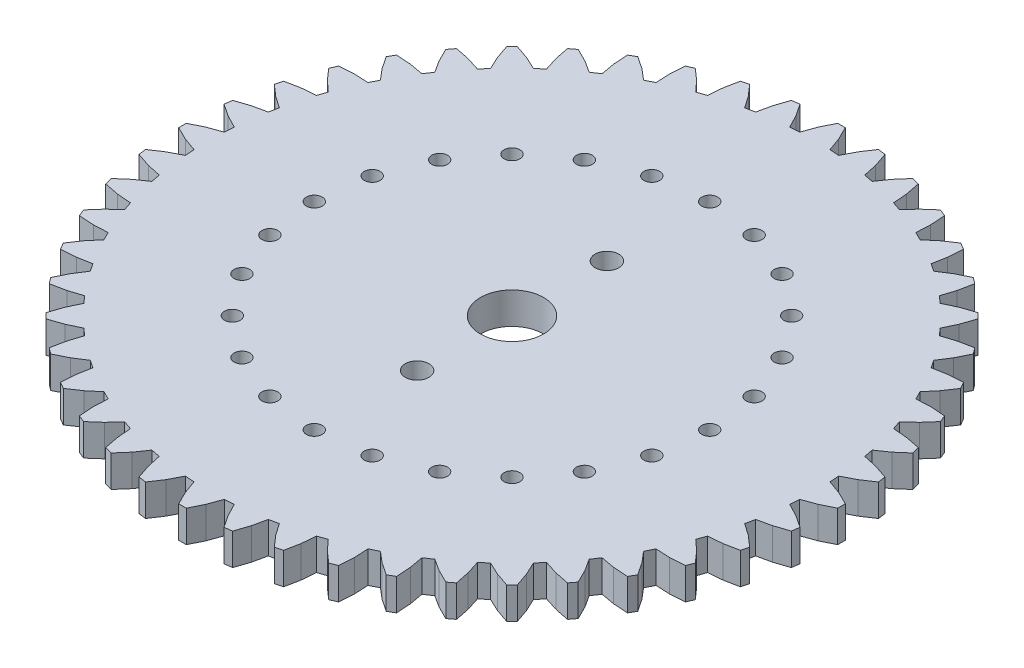
SolidWorks part; units mm, degrees
material "Brass"
ref_plane "Front Plane" through (0, 0, 0) normal (0, 0, 1) x (1, 0, 0)
ref_plane "Top Plane" through (0, 0, 0) normal (0, 1, 0) x (1, 0, 0)
ref_plane "Right Plane" through (0, 0, 0) normal (1, 0, 0) x (0, 0, -1)
sketch "Sketch5" plane through (0, 0, 0) normal (0, 1, 0) x (1, 0, 0)
  line L0 (87.3464, 51.4964) -> (89.0397, 50.8872)
  line L1 (89.0397, 50.8872) -> (90.7249, 50.062)
  line L2 (90.7249, 50.062) -> (90.7249, 49.095)
  line L3 (90.7249, 49.095) -> (89.0397, 48.2698)
  line L4 (89.0397, 48.2698) -> (87.3464, 47.6606)
  line L5 (87.3464, 47.6606) -> (87.2693, 46.4828)
  line L6 (87.2693, 46.4828) -> (88.8685, 45.6578)
  line L7 (88.8685, 45.6578) -> (90.4317, 44.6196)
  line L8 (90.4317, 44.6196) -> (90.3054, 43.6609)
  line L9 (90.3054, 43.6609) -> (88.5268, 43.0627)
  line L10 (88.5268, 43.0627) -> (86.7686, 42.6797)
  line L11 (86.7686, 42.6797) -> (86.5383, 41.5221)
  line L12 (86.5383, 41.5221) -> (88.0162, 40.4955)
  line L13 (88.0162, 40.4955) -> (89.4304, 39.2621)
  line L14 (89.4304, 39.2621) -> (89.1801, 38.328)
  line L15 (89.1801, 38.328) -> (87.3386, 37.9672)
  line L16 (87.3386, 37.9672) -> (85.5454, 37.8169)
  line L17 (85.5454, 37.8169) -> (85.1661, 36.6994)
  line L18 (85.1661, 36.6994) -> (86.4974, 35.4884)
  line L19 (86.4974, 35.4884) -> (87.7385, 34.0811)
  line L20 (87.7385, 34.0811) -> (87.3685, 33.1877)
  line L21 (87.3685, 33.1877) -> (85.4956, 33.0702)
  line L22 (85.4956, 33.0702) -> (83.6981, 33.1553)
  line L23 (83.6981, 33.1553) -> (83.1762, 32.0968)
  line L24 (83.1762, 32.0968) -> (84.3379, 30.7226)
  line L25 (84.3379, 30.7226) -> (85.3848, 29.1653)
  line L26 (85.3848, 29.1653) -> (84.9013, 28.3278)
  line L27 (84.9013, 28.3278) -> (83.0292, 28.4557)
  line L28 (83.0292, 28.4557) -> (81.2581, 28.7747)
  line L29 (81.2581, 28.7747) -> (80.6024, 27.7935)
  line L30 (80.6024, 27.7935) -> (81.575, 26.2794)
  line L31 (81.575, 26.2794) -> (82.4096, 24.5987)
  line L32 (82.4096, 24.5987) -> (81.821, 23.8315)
  line L33 (81.821, 23.8315) -> (79.9815, 24.2028)
  line L34 (79.9815, 24.2028) -> (78.2673, 24.7502)
  line L35 (78.2673, 24.7502) -> (77.4891, 23.8628)
  line L36 (77.4891, 23.8628) -> (78.2556, 22.2348)
  line L37 (78.2556, 22.2348) -> (78.8638, 20.4595)
  line L38 (78.8638, 20.4595) -> (78.18, 19.7757)
  line L39 (78.18, 19.7757) -> (76.4047, 20.3839)
  line L40 (76.4047, 20.3839) -> (74.7767, 21.1504)
  line L41 (74.7767, 21.1504) -> (73.8893, 20.3722)
  line L42 (73.8893, 20.3722) -> (74.4368, 18.658)
  line L43 (74.4368, 18.658) -> (74.808, 16.8186)
  line L44 (74.808, 16.8186) -> (74.0408, 16.2299)
  line L45 (74.0408, 16.2299) -> (72.3602, 17.0645)
  line L46 (72.3602, 17.0645) -> (70.846, 18.0371)
  line L47 (70.846, 18.0371) -> (69.8648, 17.3814)
  line L48 (69.8648, 17.3814) -> (70.1838, 15.6104)
  line L49 (70.1838, 15.6104) -> (70.3117, 13.7382)
  line L50 (70.3117, 13.7382) -> (69.4742, 13.2547)
  line L51 (69.4742, 13.2547) -> (67.9169, 14.3016)
  line L52 (67.9169, 14.3016) -> (66.5427, 15.4634)
  line L53 (66.5427, 15.4634) -> (65.4842, 14.9415)
  line L54 (65.4842, 14.9415) -> (65.5693, 13.1439)
  line L55 (65.5693, 13.1439) -> (65.4518, 11.271)
  line L56 (65.4518, 11.271) -> (64.5584, 10.901)
  line L57 (64.5584, 10.901) -> (63.1511, 12.1422)
  line L58 (63.1511, 12.1422) -> (61.9401, 13.4734)
  line L59 (61.9401, 13.4734) -> (60.8226, 13.0941)
  line L60 (60.8226, 13.0941) -> (60.6724, 11.3009)
  line L61 (60.6724, 11.3009) -> (60.3115, 9.4594)
  line L62 (60.3115, 9.4594) -> (59.3774, 9.2091)
  line L63 (59.3774, 9.2091) -> (58.144, 10.6233)
  line L64 (58.144, 10.6233) -> (57.1174, 12.1012)
  line L65 (57.1174, 12.1012) -> (55.9598, 11.8709)
  line L66 (55.9598, 11.8709) -> (55.5768, 10.1127)
  line L67 (55.5768, 10.1127) -> (54.9786, 8.3341)
  line L68 (54.9786, 8.3341) -> (54.0199, 8.2078)
  line L69 (54.0199, 8.2078) -> (52.9817, 9.771)
  line L70 (52.9817, 9.771) -> (52.1567, 11.3702)
  line L71 (52.1567, 11.3702) -> (50.979, 11.2931)
  line L72 (50.979, 11.2931) -> (50.3698, 9.5998)
  line L73 (50.3698, 9.5998) -> (49.5446, 7.9146)
  line L74 (49.5446, 7.9146) -> (48.5775, 7.9146)
  line L75 (48.5775, 7.9146) -> (47.7523, 9.5998)
  line L76 (47.7523, 9.5998) -> (47.1431, 11.2931)
  line L77 (47.1431, 11.2931) -> (45.9654, 11.3702)
  line L78 (45.9654, 11.3702) -> (45.1403, 9.771)
  line L79 (45.1403, 9.771) -> (44.1021, 8.2078)
  line L80 (44.1021, 8.2078) -> (43.1434, 8.3341)
  line L81 (43.1434, 8.3341) -> (42.5452, 10.1127)
  line L82 (42.5452, 10.1127) -> (42.1622, 11.8709)
  line L83 (42.1622, 11.8709) -> (41.0046, 12.1012)
  line L84 (41.0046, 12.1012) -> (39.978, 10.6233)
  line L85 (39.978, 10.6233) -> (38.7447, 9.2091)
  line L86 (38.7447, 9.2091) -> (37.8106, 9.4594)
  line L87 (37.8106, 9.4594) -> (37.4497, 11.3009)
  line L88 (37.4497, 11.3009) -> (37.2994, 13.0941)
  line L89 (37.2994, 13.0941) -> (36.1819, 13.4734)
  line L90 (36.1819, 13.4734) -> (34.9709, 12.1422)
  line L91 (34.9709, 12.1422) -> (33.5636, 10.901)
  line L92 (33.5636, 10.901) -> (32.6702, 11.271)
  line L93 (32.6702, 11.271) -> (32.5527, 13.1439)
  line L94 (32.5527, 13.1439) -> (32.6378, 14.9415)
  line L95 (32.6378, 14.9415) -> (31.5793, 15.4634)
  line L96 (31.5793, 15.4634) -> (30.2051, 14.3016)
  line L97 (30.2051, 14.3016) -> (28.6478, 13.2547)
  line L98 (28.6478, 13.2547) -> (27.8103, 13.7382)
  line L99 (27.8103, 13.7382) -> (27.9382, 15.6104)
  line L100 (27.9382, 15.6104) -> (28.2572, 17.3814)
  line L101 (28.2572, 17.3814) -> (27.276, 18.0371)
  line L102 (27.276, 18.0371) -> (25.7619, 17.0645)
  line L103 (25.7619, 17.0645) -> (24.0812, 16.2299)
  line L104 (24.0812, 16.2299) -> (23.314, 16.8186)
  line L105 (23.314, 16.8186) -> (23.6853, 18.658)
  line L106 (23.6853, 18.658) -> (24.2327, 20.3722)
  line L107 (24.2327, 20.3722) -> (23.3453, 21.1504)
  line L108 (23.3453, 21.1504) -> (21.7173, 20.3839)
  line L109 (21.7173, 20.3839) -> (19.9421, 19.7757)
  line L110 (19.9421, 19.7757) -> (19.2582, 20.4595)
  line L111 (19.2582, 20.4595) -> (19.8664, 22.2348)
  line L112 (19.8664, 22.2348) -> (20.6329, 23.8628)
  line L113 (20.6329, 23.8628) -> (19.8547, 24.7502)
  line L114 (19.8547, 24.7502) -> (18.1405, 24.2028)
  line L115 (18.1405, 24.2028) -> (16.3011, 23.8315)
  line L116 (16.3011, 23.8315) -> (15.7124, 24.5987)
  line L117 (15.7124, 24.5987) -> (16.547, 26.2794)
  line L118 (16.547, 26.2794) -> (17.5196, 27.7935)
  line L119 (17.5196, 27.7935) -> (16.8639, 28.7747)
  line L120 (16.8639, 28.7747) -> (15.0929, 28.4557)
  line L121 (15.0929, 28.4557) -> (13.2207, 28.3278)
  line L122 (13.2207, 28.3278) -> (12.7372, 29.1653)
  line L123 (12.7372, 29.1653) -> (13.7841, 30.7226)
  line L124 (13.7841, 30.7226) -> (14.9459, 32.0968)
  line L125 (14.9459, 32.0968) -> (14.424, 33.1553)
  line L126 (14.424, 33.1553) -> (12.6264, 33.0702)
  line L127 (12.6264, 33.0702) -> (10.7535, 33.1877)
  line L128 (10.7535, 33.1877) -> (10.3835, 34.0811)
  line L129 (10.3835, 34.0811) -> (11.6247, 35.4884)
  line L130 (11.6247, 35.4884) -> (12.9559, 36.6994)
  line L131 (12.9559, 36.6994) -> (12.5766, 37.8169)
  line L132 (12.5766, 37.8169) -> (10.7834, 37.9672)
  line L133 (10.7834, 37.9672) -> (8.9419, 38.328)
  line L134 (8.9419, 38.328) -> (8.6916, 39.2621)
  line L135 (8.6916, 39.2621) -> (10.1058, 40.4955)
  line L136 (10.1058, 40.4955) -> (11.5837, 41.5221)
  line L137 (11.5837, 41.5221) -> (11.3534, 42.6797)
  line L138 (11.3534, 42.6797) -> (9.5952, 43.0627)
  line L139 (9.5952, 43.0627) -> (7.8167, 43.6609)
  line L140 (7.8167, 43.6609) -> (7.6903, 44.6196)
  line L141 (7.6903, 44.6196) -> (9.2536, 45.6578)
  line L142 (9.2536, 45.6578) -> (10.8528, 46.4828)
  line L143 (10.8528, 46.4828) -> (10.7757, 47.6606)
  line L144 (10.7757, 47.6606) -> (9.0823, 48.2698)
  line L145 (9.0823, 48.2698) -> (7.3971, 49.095)
  line L146 (7.3971, 49.095) -> (7.3971, 50.062)
  line L147 (7.3971, 50.062) -> (9.0823, 50.8872)
  line L148 (9.0823, 50.8872) -> (10.7757, 51.4964)
  line L149 (10.7757, 51.4964) -> (10.8528, 52.6742)
  line L150 (10.8528, 52.6742) -> (9.2536, 53.4992)
  line L151 (9.2536, 53.4992) -> (7.6903, 54.5374)
  line L152 (7.6903, 54.5374) -> (7.8167, 55.4961)
  line L153 (7.8167, 55.4961) -> (9.5952, 56.0943)
  line L154 (9.5952, 56.0943) -> (11.3534, 56.4773)
  line L155 (11.3534, 56.4773) -> (11.5837, 57.6349)
  line L156 (11.5837, 57.6349) -> (10.1058, 58.6615)
  line L157 (10.1058, 58.6615) -> (8.6916, 59.8949)
  line L158 (8.6916, 59.8949) -> (8.9419, 60.829)
  line L159 (8.9419, 60.829) -> (10.7834, 61.1898)
  line L160 (10.7834, 61.1898) -> (12.5766, 61.3401)
  line L161 (12.5766, 61.3401) -> (12.9559, 62.4576)
  line L162 (12.9559, 62.4576) -> (11.6247, 63.6686)
  line L163 (11.6247, 63.6686) -> (10.3835, 65.0759)
  line L164 (10.3835, 65.0759) -> (10.7535, 65.9693)
  line L165 (10.7535, 65.9693) -> (12.6264, 66.0868)
  line L166 (12.6264, 66.0868) -> (14.424, 66.0017)
  line L167 (14.424, 66.0017) -> (14.9459, 67.0602)
  line L168 (14.9459, 67.0602) -> (13.7841, 68.4344)
  line L169 (13.7841, 68.4344) -> (12.7372, 69.9917)
  line L170 (12.7372, 69.9917) -> (13.2207, 70.8292)
  line L171 (13.2207, 70.8292) -> (15.0929, 70.7013)
  line L172 (15.0929, 70.7013) -> (16.8639, 70.3823)
  line L173 (16.8639, 70.3823) -> (17.5196, 71.3635)
  line L174 (17.5196, 71.3635) -> (16.547, 72.8776)
  line L175 (16.547, 72.8776) -> (15.7124, 74.5583)
  line L176 (15.7124, 74.5583) -> (16.3011, 75.3255)
  line L177 (16.3011, 75.3255) -> (18.1405, 74.9542)
  line L178 (18.1405, 74.9542) -> (19.8547, 74.4068)
  line L179 (19.8547, 74.4068) -> (20.6329, 75.2942)
  line L180 (20.6329, 75.2942) -> (19.8664, 76.9222)
  line L181 (19.8664, 76.9222) -> (19.2582, 78.6975)
  line L182 (19.2582, 78.6975) -> (19.9421, 79.3813)
  line L183 (19.9421, 79.3813) -> (21.7173, 78.7731)
  line L184 (21.7173, 78.7731) -> (23.3453, 78.0066)
  line L185 (23.3453, 78.0066) -> (24.2327, 78.7848)
  line L186 (24.2327, 78.7848) -> (23.6853, 80.499)
  line L187 (23.6853, 80.499) -> (23.314, 82.3384)
  line L188 (23.314, 82.3384) -> (24.0812, 82.9271)
  line L189 (24.0812, 82.9271) -> (25.7619, 82.0925)
  line L190 (25.7619, 82.0925) -> (27.276, 81.1199)
  line L191 (27.276, 81.1199) -> (28.2572, 81.7756)
  line L192 (28.2572, 81.7756) -> (27.9382, 83.5466)
  line L193 (27.9382, 83.5466) -> (27.8103, 85.4188)
  line L194 (27.8103, 85.4188) -> (28.6478, 85.9023)
  line L195 (28.6478, 85.9023) -> (30.2051, 84.8554)
  line L196 (30.2051, 84.8554) -> (31.5793, 83.6936)
  line L197 (31.5793, 83.6936) -> (32.6378, 84.2155)
  line L198 (32.6378, 84.2155) -> (32.5527, 86.0131)
  line L199 (32.5527, 86.0131) -> (32.6702, 87.886)
  line L200 (32.6702, 87.886) -> (33.5636, 88.256)
  line L201 (33.5636, 88.256) -> (34.9709, 87.0148)
  line L202 (34.9709, 87.0148) -> (36.1819, 85.6836)
  line L203 (36.1819, 85.6836) -> (37.2994, 86.0629)
  line L204 (37.2994, 86.0629) -> (37.4497, 87.8561)
  line L205 (37.4497, 87.8561) -> (37.8106, 89.6976)
  line L206 (37.8106, 89.6976) -> (38.7447, 89.9479)
  line L207 (38.7447, 89.9479) -> (39.978, 88.5337)
  line L208 (39.978, 88.5337) -> (41.0046, 87.0558)
  line L209 (41.0046, 87.0558) -> (42.1622, 87.2861)
  line L210 (42.1622, 87.2861) -> (42.5452, 89.0443)
  line L211 (42.5452, 89.0443) -> (43.1434, 90.8228)
  line L212 (43.1434, 90.8228) -> (44.1021, 90.9492)
  line L213 (44.1021, 90.9492) -> (45.1403, 89.386)
  line L214 (45.1403, 89.386) -> (45.9654, 87.7868)
  line L215 (45.9654, 87.7868) -> (47.1431, 87.8639)
  line L216 (47.1431, 87.8639) -> (47.7523, 89.5572)
  line L217 (47.7523, 89.5572) -> (48.5775, 91.2424)
  line L218 (48.5775, 91.2424) -> (49.5446, 91.2424)
  line L219 (49.5446, 91.2424) -> (50.3698, 89.5572)
  line L220 (50.3698, 89.5572) -> (50.979, 87.8639)
  line L221 (50.979, 87.8639) -> (52.1567, 87.7868)
  line L222 (52.1567, 87.7868) -> (52.9817, 89.386)
  line L223 (52.9817, 89.386) -> (54.0199, 90.9492)
  line L224 (54.0199, 90.9492) -> (54.9786, 90.8228)
  line L225 (54.9786, 90.8228) -> (55.5768, 89.0443)
  line L226 (55.5768, 89.0443) -> (55.9598, 87.2861)
  line L227 (55.9598, 87.2861) -> (57.1174, 87.0558)
  line L228 (57.1174, 87.0558) -> (58.144, 88.5337)
  line L229 (58.144, 88.5337) -> (59.3774, 89.9479)
  line L230 (59.3774, 89.9479) -> (60.3115, 89.6976)
  line L231 (60.3115, 89.6976) -> (60.6724, 87.8561)
  line L232 (60.6724, 87.8561) -> (60.8226, 86.0629)
  line L233 (60.8226, 86.0629) -> (61.9401, 85.6836)
  line L234 (61.9401, 85.6836) -> (63.1511, 87.0148)
  line L235 (63.1511, 87.0148) -> (64.5584, 88.256)
  line L236 (64.5584, 88.256) -> (65.4518, 87.886)
  line L237 (65.4518, 87.886) -> (65.5693, 86.0131)
  line L238 (65.5693, 86.0131) -> (65.4842, 84.2155)
  line L239 (65.4842, 84.2155) -> (66.5427, 83.6936)
  line L240 (66.5427, 83.6936) -> (67.9169, 84.8554)
  line L241 (67.9169, 84.8554) -> (69.4742, 85.9023)
  line L242 (69.4742, 85.9023) -> (70.3117, 85.4188)
  line L243 (70.3117, 85.4188) -> (70.1838, 83.5466)
  line L244 (70.1838, 83.5466) -> (69.8648, 81.7756)
  line L245 (69.8648, 81.7756) -> (70.846, 81.1199)
  line L246 (70.846, 81.1199) -> (72.3602, 82.0925)
  line L247 (72.3602, 82.0925) -> (74.0408, 82.9271)
  line L248 (74.0408, 82.9271) -> (74.808, 82.3384)
  line L249 (74.808, 82.3384) -> (74.4368, 80.499)
  line L250 (74.4368, 80.499) -> (73.8893, 78.7848)
  line L251 (73.8893, 78.7848) -> (74.7767, 78.0066)
  line L252 (74.7767, 78.0066) -> (76.4047, 78.7731)
  line L253 (76.4047, 78.7731) -> (78.18, 79.3813)
  line L254 (78.18, 79.3813) -> (78.8638, 78.6975)
  line L255 (78.8638, 78.6975) -> (78.2556, 76.9222)
  line L256 (78.2556, 76.9222) -> (77.4891, 75.2942)
  line L257 (77.4891, 75.2942) -> (78.2673, 74.4068)
  line L258 (78.2673, 74.4068) -> (79.9815, 74.9542)
  line L259 (79.9815, 74.9542) -> (81.821, 75.3255)
  line L260 (81.821, 75.3255) -> (82.4096, 74.5583)
  line L261 (82.4096, 74.5583) -> (81.575, 72.8776)
  line L262 (81.575, 72.8776) -> (80.6024, 71.3635)
  line L263 (80.6024, 71.3635) -> (81.2581, 70.3823)
  line L264 (81.2581, 70.3823) -> (83.0292, 70.7013)
  line L265 (83.0292, 70.7013) -> (84.9013, 70.8292)
  line L266 (84.9013, 70.8292) -> (85.3848, 69.9917)
  line L267 (85.3848, 69.9917) -> (84.3379, 68.4344)
  line L268 (84.3379, 68.4344) -> (83.1762, 67.0602)
  line L269 (83.1762, 67.0602) -> (83.6981, 66.0017)
  line L270 (83.6981, 66.0017) -> (85.4956, 66.0868)
  line L271 (85.4956, 66.0868) -> (87.3685, 65.9693)
  line L272 (87.3685, 65.9693) -> (87.7385, 65.0759)
  line L273 (87.7385, 65.0759) -> (86.4974, 63.6686)
  line L274 (86.4974, 63.6686) -> (85.1661, 62.4576)
  line L275 (85.1661, 62.4576) -> (85.5454, 61.3401)
  line L276 (85.5454, 61.3401) -> (87.3386, 61.1898)
  line L277 (87.3386, 61.1898) -> (89.1801, 60.829)
  line L278 (89.1801, 60.829) -> (89.4304, 59.8949)
  line L279 (89.4304, 59.8949) -> (88.0162, 58.6615)
  line L280 (88.0162, 58.6615) -> (86.5383, 57.6349)
  line L281 (86.5383, 57.6349) -> (86.7686, 56.4773)
  line L282 (86.7686, 56.4773) -> (88.5268, 56.0943)
  line L283 (88.5268, 56.0943) -> (90.3054, 55.4961)
  line L284 (90.3054, 55.4961) -> (90.4317, 54.5374)
  line L285 (90.4317, 54.5374) -> (88.8685, 53.4992)
  line L286 (88.8685, 53.4992) -> (87.2693, 52.6742)
  line L287 (87.2693, 52.6742) -> (87.3464, 51.4964)
  line L288 (49.061, 91.2424) -> (49.061, 7.9146) construction
  line L289 (7.3971, 49.5785) -> (90.7249, 49.5785) construction
  point P292 (49.061, 49.5785)
sketch "Sketch6" plane through (0, 0, 0) normal (0, 1, 0) x (1, 0, 0)
  line L0 (49.061, 91.2424) -> (49.061, 7.9146) construction
  circle A0 centre (49.061, 49.5785) radius 4
  dimension "D1" = 8
sketch "Sketch7" plane through (0, 0, 0) normal (0, 1, 0) x (1, 0, 0)
  line L0 (49.061, 91.2424) -> (49.061, 7.9146) construction
  line L1 (25.4921, 49.5785) -> (64.6594, 49.5785) construction
  line L2 (7.3971, 49.5785) -> (90.7249, 49.5785) construction
  circle A0 centre (49.061, 61.5785) radius 1.5
  circle A1 centre (49.061, 37.5785) radius 1.5
  dimension "D2" = 3
  dimension "D1" = 12
sketch "Sketch8" plane through (0, 0, 0) normal (0, 1, 0) x (1, 0, 0)
  line L0 (7.3971, 49.5785) -> (90.7249, 49.5785) construction
  circle A0 centre (49.061, 49.5785) radius 27
  dimension "D1" = 54
sketch "Sketch9" plane through (0, 0, 0) normal (0, 1, 0) x (1, 0, 0)
  line L0 (49.061, 91.2424) -> (49.061, 7.9146) construction
  line L1 (49.061, 74.5785) -> (49.061, 76.5785) construction
  circle A0 centre (49.061, 74.5785) radius 1
  circle A1 centre (49.061, 49.5785) radius 27 construction
  circle A2 centre (55.5315, 73.7266) radius 1
  circle A3 centre (61.561, 71.2291) radius 1
  circle A4 centre (66.7387, 67.2562) radius 1
  circle A5 centre (70.7116, 62.0785) radius 1
  circle A6 centre (73.2092, 56.049) radius 1
  circle A7 centre (74.061, 49.5785) radius 1
  circle A8 centre (73.2092, 43.108) radius 1
  circle A9 centre (70.7116, 37.0785) radius 1
  circle A10 centre (66.7387, 31.9008) radius 1
  circle A11 centre (61.561, 27.9279) radius 1
  circle A12 centre (55.5315, 25.4304) radius 1
  circle A13 centre (49.061, 24.5785) radius 1
  circle A14 centre (42.5905, 25.4304) radius 1
  circle A15 centre (36.561, 27.9279) radius 1
  circle A16 centre (31.3833, 31.9008) radius 1
  circle A17 centre (27.4104, 37.0785) radius 1
  circle A18 centre (24.9129, 43.108) radius 1
  circle A19 centre (24.061, 49.5785) radius 1
  circle A20 centre (24.9129, 56.049) radius 1
  circle A21 centre (27.4104, 62.0785) radius 1
  circle A22 centre (31.3833, 67.2562) radius 1
  circle A23 centre (36.561, 71.2291) radius 1
  circle A24 centre (42.5905, 73.7266) radius 1
  point P55 (49.061, 49.5785)
  dimension "D1" = 2
  dimension "D2" = 2
  dimension "D3" = 24
extrude "Boss-Extrude1" add sketch "Sketch8" along normal blind 4
extrude "Boss-Extrude2" add sketch "Sketch5" along normal up to surface (4 mm away) up to face at (49.061, 4, -22.5785)
extrude "Cut-Extrude1" cut sketch "Sketch6" along normal up to next
extrude "Cut-Extrude2" cut sketch "Sketch7" along normal up to next
extrude "Cut-Extrude3" cut sketch "Sketch9" along normal up to next
ref_axis "Axis1" through (49.061, 4, -49.5785) along (0, -1, 0)
